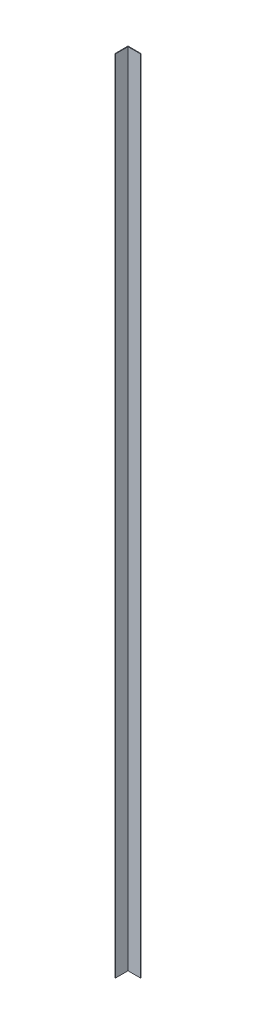
SolidWorks part; units mm, degrees
ref_plane "Front Plane" through (0, 0, 0) normal (0, 0, 1) x (1, 0, 0)
ref_plane "Top Plane" through (0, 0, 0) normal (0, 1, 0) x (1, 0, 0)
ref_plane "Right Plane" through (0, 0, 0) normal (1, 0, 0) x (0, 0, -1)
sketch "Sketch1" plane through (0, 0, 0) normal (0, 1, 0) x (1, 0, 0)
  line L0 (0, 0) -> (6.5, 0)
  line L1 (0, 0) -> (0, -6.5)
  line L4 (-0.3048, 0.3048) -> (6.5, 0.3048)
  line L5 (-0.3048, 0.3048) -> (-0.3048, -6.5)
  line L9 (-0.3048, -6.5) -> (0, -6.5)
  line L10 (6.5, 0) -> (6.5, 0.3048)
  dimension "D1" = 6.5
  dimension "D2" = 6.5
  dimension "D3" = 0.3048
extrude "Boss-Extrude1" add sketch "Sketch1" along normal blind 417.195
